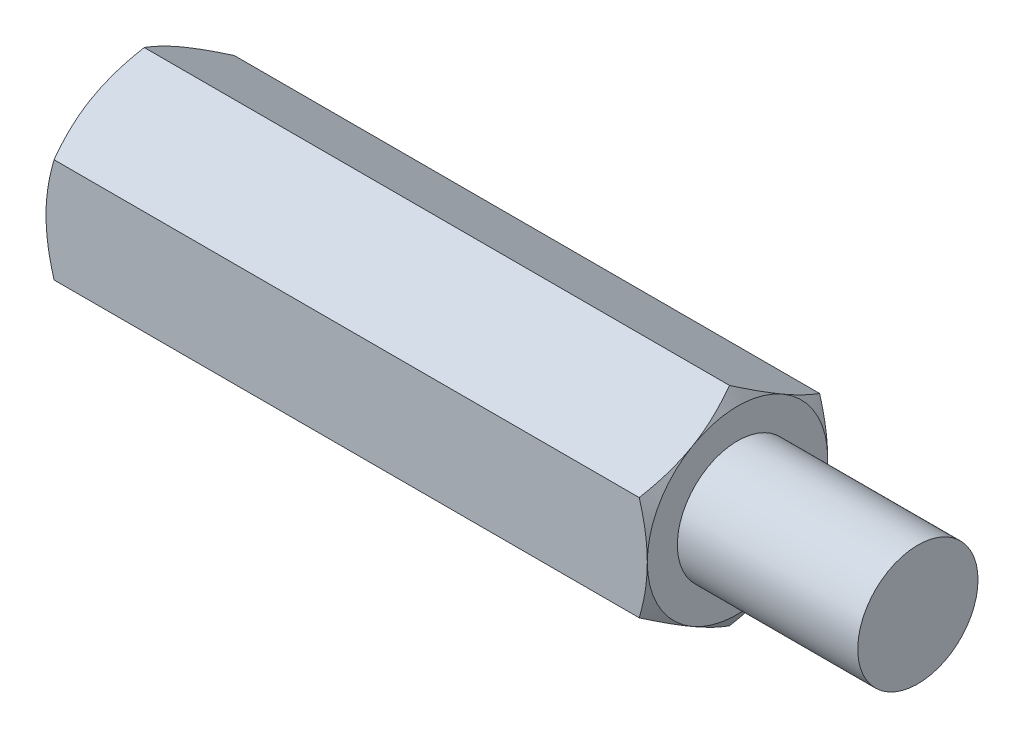
SolidWorks part; units mm, degrees
ref_plane "Front Plane" through (0, 0, 0) normal (0, 0, 1) x (1, 0, 0)
ref_plane "Top Plane" through (0, 0, 0) normal (0, 1, 0) x (1, 0, 0)
ref_plane "Right Plane" through (0, 0, 0) normal (1, 0, 0) x (0, 0, -1)
sketch "Sketch1" plane through (0, 0, 0) normal (0, 0, 1) x (1, 0, 0)
  line L0 (-14.75, 0) -> (14.75, 0) construction
  line L1 (14.75, 2) -> (14.75, -2) construction
  line L2 (-14.75, 3) -> (-14.75, -3) construction
  line L3 (-3.65, 2) -> (-3.65, -2) construction
  line L4 (-3.65, -2) -> (-14.75, -2) construction
  line L5 (-3.65, 2) -> (-14.75, 2) construction
  line L6 (-14.75, 3) -> (5.25, 3) construction
  line L7 (-14.75, -3) -> (5.25, -3) construction
  point P2 (5.25, 0)
  point P8 (-3.65, 0)
  point P13 (11.6, -2)
  dimension "Hex" = 6
  dimension "Male Thread" = 4
  dimension "A" = 20
  dimension "B" = 9.5
  dimension "C" = 11.1
  dimension "Female Thread" = 4
  dimension "D1" = 3.15
ref_plane "Plane1" through (14.75, 0, 0) normal (1, 0, 0) x (0, 0, -1)
sketch "Sketch2" plane through (14.75, 0, 0) normal (1, 0, 0) x (0, 0, -1)
  circle A0 centre (0, 0) radius 2
extrude "Extrude1" add sketch "Sketch2" against normal up to vertex (9.5 mm away) up to point (5.25, 0, 0)
sketch "Sketch3" plane through (14.75, 0, 0) normal (1, 0, 0) x (0, 0, -1)
  circle A1 centre (0, 0) radius 2
  circle A2 centre (0, 0) radius 2
  dimension "D1" = 0
curve "Helix/Spiral1" pitch 0.7 height 10.2 turns 14.5714 parameters "Male Pitch"=0.7
chamfer "Chamfer1" distance 0.525 angle 45 1 edges at (14.75, 0, -2)
sketch "Sketch4" plane through (0, 0, 0) normal (0, 0, 1) x (1, 0, 0)
  line L0 (14.75, 2) -> (15.3625, 2)
  line L1 (15.3625, 2) -> (15.1, 1.5453)
  line L2 (15.1, 1.5453) -> (15.0125, 1.5453)
  line L3 (15.0125, 1.5453) -> (14.75, 2)
  line L4 (15.0563, 1.5453) -> (15.0563, 2) construction
  line L5 (14.8812, 1.7727) -> (15.2312, 1.7727) construction
  dimension "D1" = 0.0875
  dimension "D2" = 0.35
  dimension "D3" = 60
sweep "Cut-Sweep1" [suppressed] cut profiles "Sketch4" path "Helix/Spiral1"
sketch "Sketch16" [suppressed] plane through (0, 0, 0) normal (0, 0, 1) x (1, 0, 0)
  line L0 (5.25, 1.5428) -> (6.475, 1.5428)
  line L1 (6.475, 1.5428) -> (6.9322, 2)
  line L2 (6.9322, 2) -> (5.25, 2)
  line L3 (5.25, 2) -> (5.25, 1.5428)
  line L4 (14.75, 2) -> (15.3625, 2) construction
  line L5 (0, 0) -> (14.75, 0) construction
  line L6 (14.75, -1.475) -> (14.75, 1.475) construction
  dimension "D1" = 1.225
  dimension "D2" = 45
  dimension "D3" = 0.0025
revolve "Cut-Revolve1" [suppressed] cut sketch "Sketch16" angle 360 about L5
ref_plane "Plane2" through (5.25, 0, 0) normal (1, 0, 0) x (0, 0, -1)
sketch "Sketch7" plane through (5.25, 0, 0) normal (1, 0, 0) x (0, 0, -1)
  line L1 (0, 3.4641) -> (-3, 1.7321)
  line L2 (-3, 1.7321) -> (-3, -1.7321)
  line L3 (-3, -1.7321) -> (0, -3.4641)
  line L4 (0, -3.4641) -> (3, -1.7321)
  line L5 (3, -1.7321) -> (3, 1.7321)
  line L6 (3, 1.7321) -> (0, 3.4641)
  circle A0 centre (0, 0) radius 3 construction
extrude "Extrude4" add sketch "Sketch7" against normal up to vertex (20 mm away) up to point (-14.75, 0, 0)
sketch "Sketch17" plane through (0, 0, 0) normal (0, 0, 1) x (1, 0, 0)
  line L0 (-14.75, -3.4641) -> (5.25, -3.4641) construction
  line L1 (-14.75, 3.4641) -> (5.25, 3.4641) construction
  line L2 (-14.75, -3.4641) -> (5.25, -3.4641)
  line L3 (-14.75, 3.4641) -> (5.25, 3.4641)
sketch "Sketch8" plane through (-14.75, 0, 0) normal (-1, 0, 0) x (0, 0, 1)
  circle A0 centre (0, 0) radius 3 construction
  circle A1 centre (0, 0) radius 3
extrude "Extrude5" cut sketch "Sketch8" against normal through all draft 60 flip side to cut
sketch "Sketch9" plane through (5.25, 0, 0) normal (1, 0, 0) x (0, 0, -1)
  circle A0 centre (0, 0) radius 3 construction
  circle A1 centre (0, 0) radius 3
extrude "Extrude6" cut sketch "Sketch9" against normal through all draft 60 flip side to cut
sketch "Sketch10" plane through (-14.75, 0, 0) normal (-1, 0, 0) x (0, 0, 1)
  line L0 (0, 0) -> (-1.4142, 1.4142) construction
  line L1 (0, 0) -> (-2, 0) construction
  circle A0 centre (0, 0) radius 2
  dimension "D1" = 45
extrude "Extrude7" cut sketch "Sketch10" against normal up to vertex (11.1 mm away) up to point (-3.65, 0, 0)
sketch "Sketch11" plane through (-14.75, 0, 0) normal (-1, 0, 0) x (0, 0, 1)
  circle A0 centre (0, 0) radius 2 construction
  circle A1 centre (0, 0) radius 2
curve "Helix/Spiral2" pitch 0.7 height 11.1 radius 2 centre (-14.75, 0, 0) axis (1, 0, 0) start towards (0, 1, 0) parameters "Female Pitch"=0.7
sketch "Sketch12" plane through (0, 0, 0) normal (0, 0, 1) x (1, 0, 0)
  line L0 (-15.3625, 2) -> (-15.1, 1.5453)
  line L1 (-15.1, 1.5453) -> (-15.0125, 1.5453)
  line L2 (-15.0125, 1.5453) -> (-14.75, 2)
  line L3 (-15.3625, 2) -> (-14.75, 2)
  line L4 (-15.0562, 1.5453) -> (-15.0562, 2) construction
  line L5 (-14.75, 3) -> (-14.75, -3) construction
  line L6 (-15.2312, 1.7727) -> (-14.8812, 1.7727) construction
  dimension "D1" = 60
  dimension "D2" = 0.0875
  dimension "D3" = 0.35
sweep "Sweep3" add profiles "Sketch12" path "Helix/Spiral2"
sketch "Sketch13" plane through (-14.75, 0, 0) normal (-1, 0, 0) x (0, 0, 1)
  circle A2 centre (0, 0) radius 2.0508
  circle A3 centre (0, 0) radius 2.0508
  dimension "D1" = 0.0508
extrude "Extrude8" cut sketch "Sketch13" along normal through all and the other way through all draft 45
sketch "Sketch20" plane through (14.75, 0, 0) normal (1, 0, 0) x (0, 0, -1)
  circle A0 centre (0, 0) radius 5
  dimension "D1" = 10
extrude "Cut-Extrude6" cut sketch "Sketch20" against normal offset from surface (3.5 mm away) 6 up to face at (5.25, 0, -2)
equation "\"D3@Helix/Spiral1\" = \"B@Sketch1\"+\"Male Pitch@Helix/Spiral1\"*1"
equation "\"D1@Chamfer1\" = \"Male Pitch@Helix/Spiral1\"*.750"
equation "\"D1@Sketch4\" = \"Male Pitch@Helix/Spiral1\"*.125"
equation "\"D2@Sketch4\" = \"Male Pitch@Helix/Spiral1\"*.5"
equation "\"D2@Sketch12\" = \"Male Pitch@Helix/Spiral1\"*.125"
equation "\"D3@Sketch12\" = \"Male Pitch@Helix/Spiral1\"*.5"
equation "\"D3@Helix/Spiral2\" = \"C@Sketch1\""
equation "\"Female Thread@Sketch1\" = \"Male Thread@Sketch1\""
equation "\"Female Pitch@Helix/Spiral2\" = \"Male Pitch@Helix/Spiral1\""
equation "\"D1@Sketch16\" = \"Male Pitch@Helix/Spiral1\"*1.75"
equation "\"D1@Sketch1\" = \"Male Pitch@Helix/Spiral1\"*4.5"
